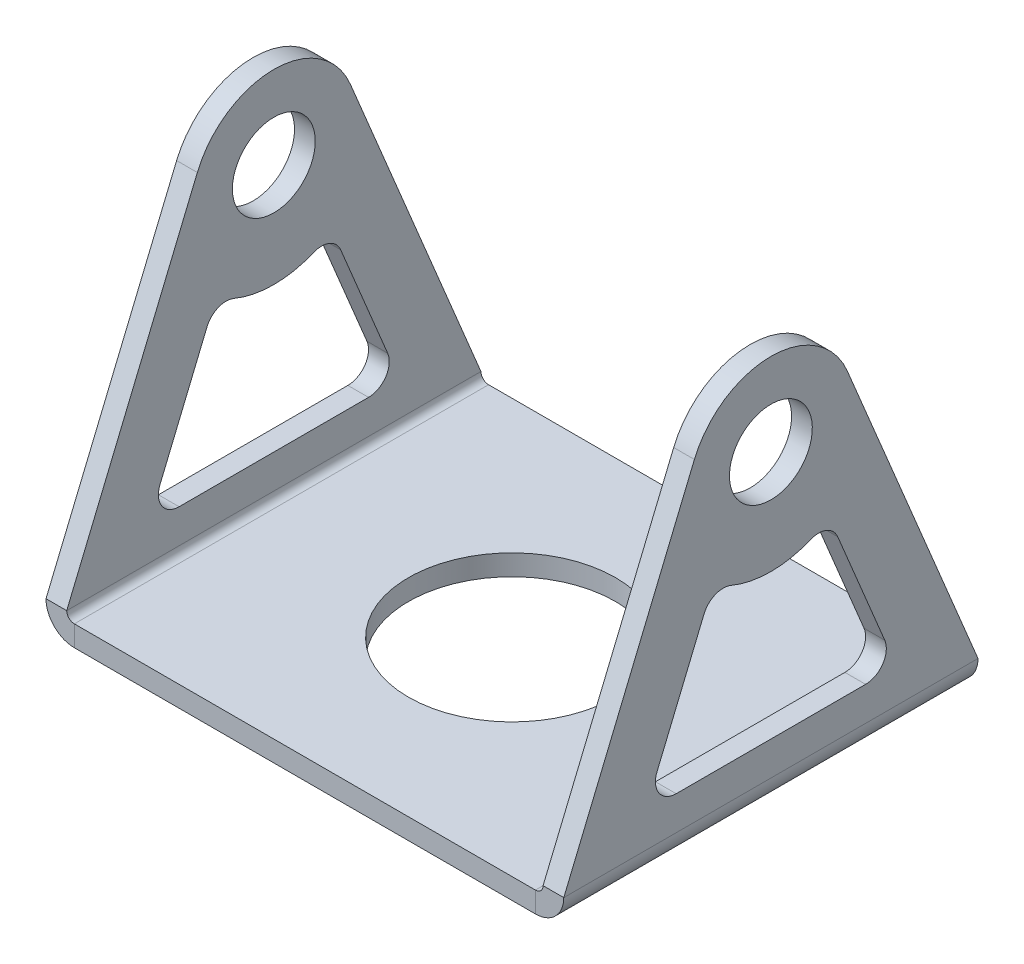
SolidWorks part; units mm, degrees
note: The reader was unsure of these and kept them because the rebuilt part matched: flange length of "Edge-Flange1".
ref_plane "Front Plane" through (0, 0, 0) normal (0, 0, 1) x (1, 0, 0)
ref_plane "Top Plane" through (0, 0, 0) normal (0, 1, 0) x (1, 0, 0)
ref_plane "Right Plane" through (0, 0, 0) normal (1, 0, 0) x (0, 0, -1)
sketch "Sketch1" plane through (0, 0, 0) normal (0, 1, 0) x (1, 0, 0)
  line L1 (-25, -20) -> (25, -20)
  line L2 (-25, -20) -> (-25, 20)
  line L3 (-25, 20) -> (25, 20)
  line L4 (25, -20) -> (25, 20)
  line L5 (-25, -20) -> (25, 20) construction
  line L6 (-25, 20) -> (25, -20) construction
  point P0 (0, 0)
  dimension "D1" = 50
  dimension "D2" = 40
base flange "Base-Flange1" sketch "Sketch1" thickness 2 reverse thickness direction no parameters "D1"=0.7366
edge flange "Edge-Flange1" sketch "Sketch13" flange angle 90 flange length 38 flange position material inside bend radius 0.7366 thickness 2 relief rectangular parameters "D6"=10
sketch "Sketch13" plane through (-25, 0, 0) normal (-1, 0, 0) x (0, 0, 1)
  line L2 (-20, 0) -> (-20, 36)
  line L3 (-20, 36) -> (20, 36)
  line L4 (20, 36) -> (20, 0)
  line L11 (-20, 0) -> (20, 0) construction
  line L12 (-20, 0) -> (20, 0)
  dimension "D1" = 36
bend "EdgeBend1" bend radius 0.7366 bend angle 90 parameters "D5"=1
sketch "Sketch14" plane through (-25, 0, 0) normal (-1, 0, 0) x (0, 0, 1)
  line L0 (20, 36) -> (-20, 36) construction
  line L1 (-7.3869, 31.0714) -> (-20, 0.7366)
  line L2 (0, 28) -> (0, 9.77) construction
  line L3 (7.3869, 31.0714) -> (20, 0.7366)
  line L4 (20, -2) -> (-20, -2) construction
  line L16 (-20, 0.7366) -> (20, 0.7366)
  line L17 (20, 0.7366) -> (20, 36)
  line L18 (20, 36) -> (-20, 36)
  line L19 (-20, 36) -> (-20, 0.7366)
  line L24 (-20, 0.7366) -> (20, 0.7366)
  line L25 (-12.1451, 4) -> (12.1451, 4)
  line L26 (20, 0.7366) -> (20, 36)
  line L27 (20, 36) -> (-20, 36)
  line L28 (5.6085, 19.7208) -> (12.1451, 4)
  line L29 (-5.6085, 19.7208) -> (-12.1451, 4)
  line L30 (-20, 36) -> (-20, 0.7366)
  circle A0 centre (0, 28) radius 8
  circle A1 centre (0, 28) radius 4
  arc A2 (-5.6085, 19.7208) -> (5.6085, 19.7208) centre (0, 28) ccw
  circle A4 centre (0, 28) radius 10 construction
  dimension "D1" = 16
  dimension "D2" = 8
  dimension "D3" = 0
  dimension "D4" = 6
  dimension "D6" = 6
  dimension "D7" = 6
  dimension "D5" = 6
extrude "Cut-Extrude2" cut sketch "Sketch14" against normal blind 10
fillet "Fillet1" radius 2 4 edges at (-24, 4, 12.1451) (-24, 19.7208, -5.6085) (-24, 19.7208, 5.6085) (-24, 4, -12.1451)
mirror "Mirror2" about plane through (0, 0, 0) normal (1, 0, 0) of "Fillet1", "Edge-Flange1", "Cut-Extrude2"
bend "MirrorBend1" bend radius 0.7366 bend angle 90 parameters "D5"=2
sketch "Sketch23" plane through (0, 0, 0) normal (0, 1, 0) x (1, 0, 0)
  circle A0 centre (0, 0) radius 10
  dimension "D1" = 20
extrude "Cut-Extrude3" cut sketch "Sketch23" against normal blind 10
sketch "Bend-Lines1" [suppressed] plane through (0, 0, 0) normal (0, 1, 0) x (1, 0, 0)
sketch "Bounding-Box1" [suppressed] plane through (0, 0, 0) normal (0, 1, 0) x (1, 0, 0)
sheet metal parameters "Sheet-Metal1" thickness 2 parameters "D1"=0.7366
flat pattern "Flat-Pattern1" [suppressed]
sketch "Bend-Lines2" plane through (0, 0, 0) normal (0, 1, 0) x (1, 0, 0)
sketch3d "Bounding-Box2" [suppressed]
  line L0 (25, 20, 0) -> (-25, 20, 0) construction
  line L1 (25, -20, 0) -> (-25, -20, 0) construction
  line L2 (25, 20, 0) -> (25, -20, 0) construction
  line L3 (-25, 20, 0) -> (-25, -20, 0) construction
sheet metal parameters "Sheet-Metal3" thickness 2 parameters "D1"=0.7366
flat pattern "Flat-Pattern1"
sketch "Bend-Lines2" plane through (0, 0, 0) normal (0, 1, 0) x (1, 0, 0)
  line L0 (-23.6273, 20) -> (-23.6273, -20) construction
  line L1 (-23.6273, 20) -> (-23.6273, -20) construction
sketch3d "Bounding-Box2" [suppressed]
  line L0 (25, 20, 0) -> (-56.2546, 20, 0) construction
  line L1 (25, -20, 0) -> (-56.2546, -20, 0) construction
  line L2 (25, 20, 0) -> (25, -20, 0) construction
  line L3 (-56.2546, 20, 0) -> (-56.2546, -20, 0) construction
bend of the flat pattern "Flatten-<EdgeBend1>1"
sheet metal parameters "Sheet-Metal4" thickness 2 parameters "D1"=0.7366
flat pattern "Flat-Pattern1"
sketch "Bend-Lines2" plane through (0, 0, 0) normal (0, 1, 0) x (1, 0, 0)
  line L0 (-23.6273, 20) -> (-23.6273, -20) construction
  line L1 (-23.6273, 20) -> (-23.6273, -20) construction
sketch3d "Bounding-Box2" [suppressed]
  line L0 (-56.2546, 20, 0) -> (25, 20, 0) construction
  line L1 (-56.2546, -20, 0) -> (25, -20, 0) construction
  line L2 (-56.2546, 20, 0) -> (-56.2546, -20, 0) construction
  line L3 (25, 20, 0) -> (25, -20, 0) construction
bend of the flat pattern "Flatten-<EdgeBend1>1"
sheet metal parameters "Sheet-Metal5" thickness 2 parameters "D1"=0.7366
flat pattern "Flat-Pattern5"
sketch "Bend-Lines3" plane through (0, 0, 0) normal (0, 1, 0) x (1, 0, 0)
  line L0 (-23.6273, -20) -> (-23.6273, 20) construction
  line L1 (-23.6273, -20) -> (-23.6273, 20) construction
sketch3d "Bounding-Box3" [suppressed]
  line L0 (-25, 20, 0) -> (24.9912, 20, 0) construction
  line L1 (-25, -20, 0) -> (24.9912, -20, 0) construction
  line L2 (-25, 20, 0) -> (-25, -20, 0) construction
  line L3 (24.9912, 20, 0) -> (24.9912, -20, 0) construction
bend of the flat pattern "Flatten-<EdgeBend1>2"
sheet metal parameters "Sheet-Metal6" thickness 2 parameters "D1"=0.7366
flat pattern "Flat-Pattern6"
sketch "Bend-Lines4" plane through (0, 0, 0) normal (0, 1, 0) x (1, 0, 0)
sketch3d "Bounding-Box4" [suppressed]
  line L0 (-20, 0.7366, 0) -> (-20, 32, 0) construction
  line L1 (0, 0.7366, 0) -> (0, 32, 0) construction
  line L2 (-20, 0.7366, 0) -> (0, 0.7366, 0) construction
  line L3 (-20, 32, 0) -> (0, 32, 0) construction
sheet metal parameters "Sheet-Metal7" thickness 2 parameters "D1"=0.7366
flat pattern "Flat-Pattern1"
sketch "Bend-Lines2" plane through (-25, 0, 0) normal (-1, 0, 0) x (0, 0, 1)
  line L0 (20, -0.6273) -> (-20, -0.6273) construction
  line L1 (20, -0.6273) -> (-20, -0.6273) construction
sketch3d "Bounding-Box2" [suppressed]
  line L0 (20, -49.2546, 0) -> (20, 35.9999, 0) construction
  line L1 (-20, -49.2546, 0) -> (-20, 35.9999, 0) construction
  line L2 (20, -49.2546, 0) -> (-20, -49.2546, 0) construction
  line L3 (20, 35.9999, 0) -> (-20, 35.9999, 0) construction
bend of the flat pattern "Flatten-<EdgeBend1>3"
sheet metal parameters "Sheet-Metal8" thickness 2 parameters "D1"=0.7366
flat pattern "Flat-Pattern8"
sketch "Bend-Lines6" plane through (0, 0, 0) normal (0, 1, 0) x (1, 0, 0)
sketch3d "Bounding-Box6" [suppressed]
  line L0 (4.0159, 27.9836, 0) -> (-3.9838, 28.0157, 0) construction
  line L1 (3.9838, 19.984, 0) -> (-4.0159, 20.0161, 0) construction
  line L2 (4.0159, 27.9836, 0) -> (3.9838, 19.984, 0) construction
  line L3 (-3.9838, 28.0157, 0) -> (-4.0159, 20.0161, 0) construction
sheet metal parameters "Sheet-Metal9" thickness 2 parameters "D1"=0.7366
flat pattern "Flat-Pattern1"
sketch "Bend-Lines2" plane through (-25, 0, 0) normal (-1, 0, 0) x (0, 0, 1)
  line L0 (20, -0.6273) -> (-20, -0.6273) construction
  line L1 (20, -0.6273) -> (-20, -0.6273) construction
  line L2 (20, -47.882) -> (-20, -47.882) construction
  line L3 (20, -47.882) -> (-20, -47.882) construction
sketch3d "Bounding-Box2" [suppressed]
  line L0 (-20, -84.5092, 0) -> (-20, 35.9999, 0) construction
  line L1 (20, -84.5092, 0) -> (20, 35.9999, 0) construction
  line L2 (-20, -84.5092, 0) -> (20, -84.5092, 0) construction
  line L3 (-20, 35.9999, 0) -> (20, 35.9999, 0) construction
bend of the flat pattern "Flatten-<EdgeBend1>3"
bend of the flat pattern "Flatten-<MirrorBend1>1"
sheet metal parameters "Sheet-Metal10" thickness 2 parameters "D1"=0.7366
flat pattern "Flat-Pattern1"
sketch "Bend-Lines2" plane through (-25, 0, 0) normal (-1, 0, 0) x (0, 0, 1)
  line L0 (20, -0.6273) -> (-20, -0.6273) construction
  line L1 (20, -0.6273) -> (-20, -0.6273) construction
  line L2 (20, -47.882) -> (-20, -47.882) construction
  line L3 (20, -47.882) -> (-20, -47.882) construction
sketch3d "Bounding-Box2" [suppressed]
  line L0 (-20, -84.5093, 0) -> (-20, 36, 0) construction
  line L1 (20, -84.5093, 0) -> (20, 36, 0) construction
  line L2 (-20, -84.5093, 0) -> (20, -84.5093, 0) construction
  line L3 (-20, 36, 0) -> (20, 36, 0) construction
bend of the flat pattern "Flatten-<EdgeBend1>3"
bend of the flat pattern "Flatten-<MirrorBend1>1"
